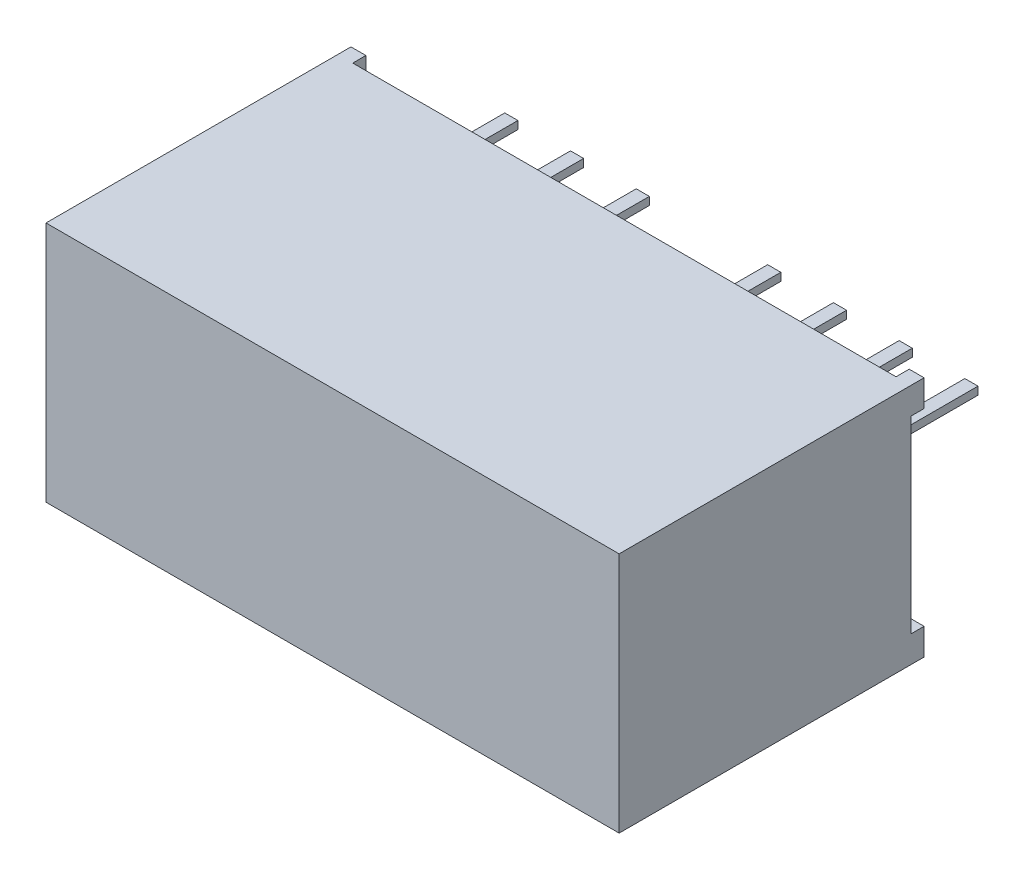
SolidWorks part; units mm, degrees
ref_plane "Front" through (0, 0, 0) normal (0, 0, 1) x (1, 0, 0)
ref_plane "Top" through (0, 0, 0) normal (0, 1, 0) x (1, 0, 0)
ref_plane "Right" through (0, 0, 0) normal (1, 0, 0) x (0, 0, -1)
sketch "Sketch2" plane through (0, 0, 0) normal (0, 1, 0) x (1, 0, 0)
  line L1 (0, 0) -> (21.8, 0)
  line L2 (0, 0) -> (0, 11.1)
  line L3 (0, 11.1) -> (21.8, 11.1)
  line L4 (21.8, 0) -> (21.8, 11.1)
  dimension "D1" = 11.1
  dimension "D2" = 21.8
extrude "Boss-Extrude1" add sketch "Sketch2" along normal blind 9.2
sketch "Sketch3" plane through (0, 0, -11.1) normal (0, 0, -1) x (-1, 0, 0)
  line L0 (0, 5.7) -> (-21.8, 5.7) construction
  line L1 (0, 9.2) -> (0, 0) construction
  line L2 (-21.8, 9.2) -> (-21.8, 0) construction
  line L3 (-21.8, 9.2) -> (0, 9.2) construction
  line L4 (-1.75, 5.85) -> (-2.25, 5.85)
  line L5 (-1.75, 5.85) -> (-1.75, 5.55)
  line L6 (-1.75, 5.55) -> (-2.25, 5.55)
  line L7 (-2.25, 5.85) -> (-2.25, 5.55)
  line L8 (-1.75, 5.85) -> (-2.25, 5.55) construction
  line L9 (-1.75, 5.55) -> (-2.25, 5.85) construction
  point P6 (-2, 5.7)
  dimension "D1" = 0.5
  dimension "D2" = 0.3
  dimension "D3" = 2
  dimension "D4" = 3.5
extrude "Boss-Extrude2" add sketch "Sketch3" along normal blind 4.6 separate body
pattern_linear "LPattern1" count 8 spacing 2.5 along (1, 0, 0) skipping (3, 0) of "Boss-Extrude2"
sketch "Sketch4" plane through (0, 0, -11.1) normal (0, 0, -1) x (-1, 0, 0)
  line L1 (0, 0) -> (-0.5673, 0)
  line L2 (0, 0) -> (0, 1.0135)
  line L3 (0, 1.0135) -> (-0.5673, 1.0135)
  line L4 (-0.5673, 0) -> (-0.5673, 1.0135)
extrude "Boss-Extrude3" add sketch "Sketch4" along normal blind 0.5
ref_plane "Plane1" through (0, 4.6, 0) normal (0, -1, 0) x (-1, 0, 0)
ref_plane "Plane2" through (10.9, 0, 0) normal (1, 0, 0) x (0, 0, -1)
mirror "Mirror1" about plane through (10.9, 0, 0) normal (1, 0, 0) of "Boss-Extrude3"
mirror "Mirror2" about plane through (0, 4.6, 0) normal (0, -1, 0) of "Mirror1"
sketch "Sketch5" plane through (0, 0, 0) normal (0, -1, 0) x (1, 0, 0)
  circle A0 centre (1.9954, -9.8874) radius 0.53
  point P2 (1.9954, -9.8874)
extrude "Cut-Extrude1" cut sketch "Sketch5" against normal blind 0.2
ref_plane "Plane3" through (2, 0, 0) normal (-1, 0, 0) x (0, 0, 1)
ref_plane "Plane4" through (0, 5.7, 0) normal (0, -1, 0) x (-1, 0, 0)
ref_axis "Axis1" through (2, 5.7, -15.93) along (0, 0, 1)
ref_point "Point1"
